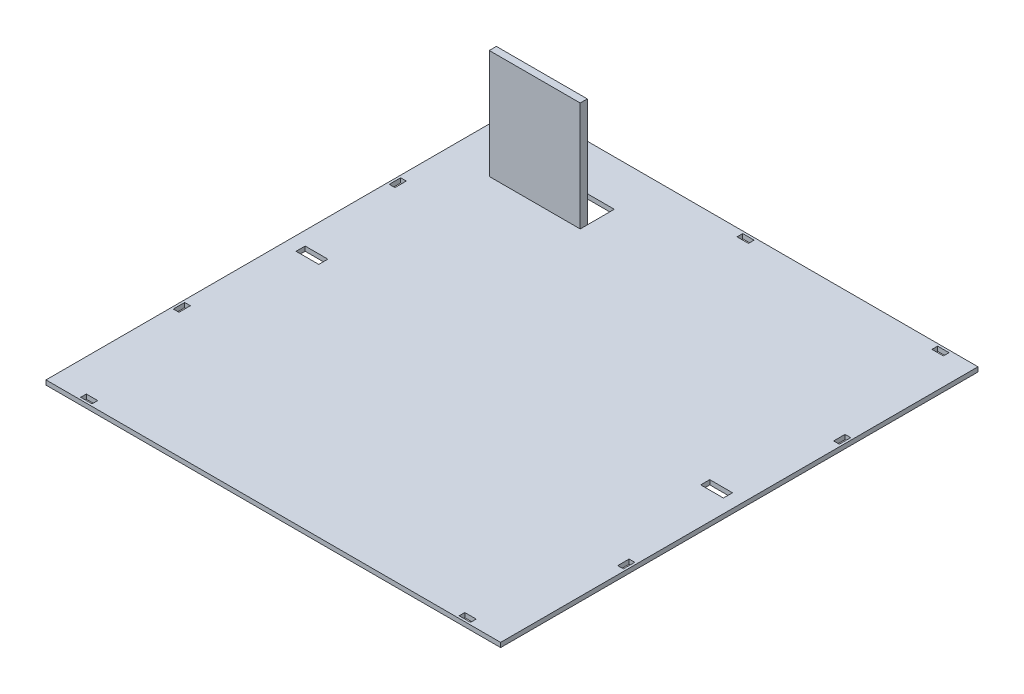
SolidWorks part; units mm, degrees
material "ABS"
ref_plane "Front Plane" through (0, 0, 0) normal (0, 0, 1) x (1, 0, 0)
ref_plane "Top Plane" through (0, 0, 0) normal (0, 1, 0) x (1, 0, 0)
ref_plane "Right Plane" through (0, 0, 0) normal (1, 0, 0) x (0, 0, -1)
sketch "Sketch1" plane through (0, 0, 0) normal (0, 1, 0) x (1, 0, 0)
  line L0 (-80, 73.1246) -> (-40, 73.1246)
  line L1 (100, 105) -> (-100, 105)
  line L2 (100, 105) -> (100, -105)
  line L3 (100, -105) -> (-100, -105)
  line L4 (-100, 105) -> (-100, -105)
  line L5 (100, 105) -> (-100, -105) construction
  line L6 (100, -105) -> (-100, 105) construction
  line L11 (94, 3) -> (84, 3)
  line L12 (94, 3) -> (94, -1)
  line L13 (94, -1) -> (84, -1)
  line L14 (84, 3) -> (84, -1)
  line L15 (94, 3) -> (84, -1) construction
  line L16 (94, -1) -> (84, 3) construction
  line L17 (-94, -1) -> (-84, -1)
  line L18 (-94, -1) -> (-94, 3)
  line L19 (-94, 3) -> (-84, 3)
  line L20 (-84, -1) -> (-84, 3)
  line L21 (-94, -1) -> (-84, 3) construction
  line L22 (-94, 3) -> (-84, -1) construction
  line L27 (-80, 70) -> (-40, 70)
  line L28 (-80, 70) -> (-80, 85)
  line L33 (-80, 85) -> (-40, 85)
  line L34 (-40, 70) -> (-40, 85)
  line L35 (85.75, -104) -> (80.75, -104)
  line L36 (85.75, -104) -> (85.75, -101.5)
  line L37 (85.75, -101.5) -> (80.75, -101.5)
  line L38 (80.75, -104) -> (80.75, -101.5)
  line L39 (85.75, -104) -> (80.75, -101.5) construction
  line L40 (85.75, -101.5) -> (80.75, -104) construction
  line L41 (-2.5, 101.5) -> (2.5, 101.5)
  line L42 (-2.5, 101.5) -> (-2.5, 104)
  line L43 (-2.5, 104) -> (2.5, 104)
  line L44 (2.5, 101.5) -> (2.5, 104)
  line L45 (-2.5, 101.5) -> (2.5, 104) construction
  line L46 (-2.5, 104) -> (2.5, 101.5) construction
  line L47 (-85.75, -104) -> (-80.75, -104)
  line L48 (-85.75, -104) -> (-85.75, -101.5)
  line L49 (-85.75, -101.5) -> (-80.75, -101.5)
  line L50 (-80.75, -104) -> (-80.75, -101.5)
  line L51 (-85.75, -104) -> (-80.75, -101.5) construction
  line L52 (-85.75, -101.5) -> (-80.75, -104) construction
  line L53 (-80.75, 104) -> (-85.75, 104)
  line L54 (-80.75, 104) -> (-80.75, 101.5)
  line L55 (-80.75, 101.5) -> (-85.75, 101.5)
  line L56 (-85.75, 104) -> (-85.75, 101.5)
  line L57 (-80.75, 104) -> (-85.75, 101.5) construction
  line L58 (-80.75, 101.5) -> (-85.75, 104) construction
  line L59 (83.25, 101.5) -> (88.25, 101.5)
  line L60 (83.25, 101.5) -> (83.25, 104)
  line L61 (83.25, 104) -> (88.25, 104)
  line L62 (88.25, 101.5) -> (88.25, 104)
  line L63 (83.25, 101.5) -> (88.25, 104) construction
  line L64 (83.25, 104) -> (88.25, 101.5) construction
  line L65 (99, -45) -> (96.5, -45)
  line L66 (99, -45) -> (99, -50)
  line L67 (99, -50) -> (96.5, -50)
  line L68 (96.5, -45) -> (96.5, -50)
  line L69 (99, -45) -> (96.5, -50) construction
  line L70 (99, -50) -> (96.5, -45) construction
  line L71 (99, 50) -> (96.5, 50)
  line L72 (99, 50) -> (99, 45)
  line L73 (99, 45) -> (96.5, 45)
  line L74 (96.5, 50) -> (96.5, 45)
  line L75 (99, 50) -> (96.5, 45) construction
  line L76 (99, 45) -> (96.5, 50) construction
  line L77 (-99, -45) -> (-96.5, -45)
  line L78 (-99, -45) -> (-99, -50)
  line L79 (-99, -50) -> (-96.5, -50)
  line L80 (-96.5, -45) -> (-96.5, -50)
  line L81 (-99, -45) -> (-96.5, -50) construction
  line L82 (-99, -50) -> (-96.5, -45) construction
  line L83 (-99, 45) -> (-96.5, 45)
  line L84 (-99, 45) -> (-99, 50)
  line L85 (-99, 50) -> (-96.5, 50)
  line L86 (-96.5, 45) -> (-96.5, 50)
  line L87 (-99, 45) -> (-96.5, 50) construction
  line L88 (-99, 50) -> (-96.5, 45) construction
  line L89 (-80, 70) -> (-40, 85) construction
  line L90 (-80, 85) -> (-40, 70) construction
  point P0 (0, 0)
  point P6 (89, 1)
  point P11 (-60, 77.5)
  point P23 (-89, 1)
  point P38 (83.25, -102.75)
  point P43 (0, 102.75)
  point P48 (-83.25, -102.75)
  point P53 (-83.25, 102.75)
  point P58 (85.75, 102.75)
  point P59 (97.75, -47.5)
  point P68 (97.75, -45)
  point P69 (97.75, 47.5)
  point P74 (-97.75, -47.5)
  point P79 (-97.75, 47.5)
  dimension "D7" = 20
  dimension "D8" = 20
  dimension "D9" = 15
  dimension "D11" = 1
  dimension "D17" = 10
  dimension "D1" = 200
  dimension "D2" = 210
  dimension "D6" = 104
  dimension "D10" = 40
  dimension "D16" = 6
  dimension "D18" = 4
  dimension "D19" = 104
  dimension "D20" = 6
  dimension "D21" = 4
  dimension "D22" = 10
  dimension "D31" = 14.25
  dimension "D32" = 1
  dimension "D33" = 5
  dimension "D34" = 2.5
  dimension "D36" = 100
  dimension "D37" = 5
  dimension "D38" = 2.5
  dimension "D39" = 1
  dimension "D40" = 14.25
  dimension "D41" = 5
  dimension "D42" = 2.5
  dimension "D43" = 14.25
  dimension "D44" = 1
  dimension "D45" = 5
  dimension "D46" = 2.5
  dimension "D47" = 14.25
  dimension "D48" = 1
  dimension "D49" = 5
  dimension "D50" = 2.5
  dimension "D51" = 1
  dimension "D52" = 5
  dimension "D53" = 2.5
  dimension "D54" = 55
  dimension "D55" = 55
  dimension "D56" = 1
  dimension "D57" = 5
  dimension "D58" = 2.5
  dimension "D59" = 1
  dimension "D60" = 55
  dimension "D61" = 2.5
  dimension "D62" = 5
  dimension "D63" = 55
  dimension "D64" = 1
  dimension "D65" = 2.5
  dimension "D66" = 5
extrude "MainBody" add sketch "Sketch1" along normal blind 2 contours L1 L4 L3 L2 L86 L83 L84 L85 L74 L71 L72 L73 L68 L65 L66 L67 L62 L59 L60 L61 L56 L53 L54 L55 L50 L47 L48 L49 L44 L41 L42 L43 L20 L17 L18 L19 L14 L11 L12 L13 L35 region at (0.8729, 0, 1.1615)
extrude "Boss-Extrude1" add sketch "Sketch1<8>" along normal blind 50 contours L27 L34 L0 L28 region at (-60, 0, -71.5623)
sketch "Sketch1<8>" plane through (0, 0, 0) normal (0, 1, 0) x (1, 0, 0) same geometry as "Sketch1"
